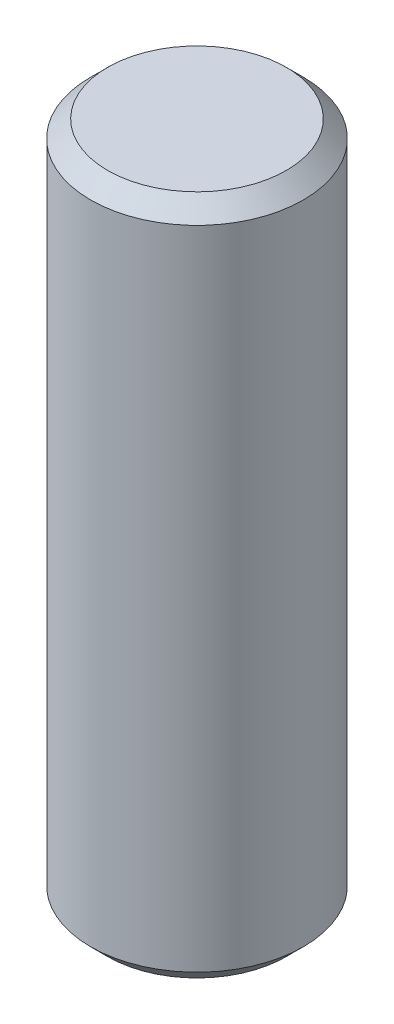
SolidWorks part; units mm, degrees
ref_plane "Front Plane" through (0, 0, 0) normal (0, 0, 1) x (1, 0, 0)
ref_plane "Top Plane" through (0, 0, 0) normal (0, 1, 0) x (1, 0, 0)
ref_plane "Right Plane" through (0, 0, 0) normal (1, 0, 0) x (0, 0, -1)
sketch "Sketch1" plane through (0, 0, 0) normal (0, 1, 0) x (1, 0, 0)
  circle A0 centre (0, 0) radius 1.5875
  dimension "D1" = 3.175
extrude "Boss-Extrude1" add sketch "Sketch1" along normal blind 5.08 and the other way blind 5.08
chamfer "Chamfer1" distance 0.254 angle 45 2 edges at (0, -5.08, 1.5875) (0, 5.08, 1.5875)
